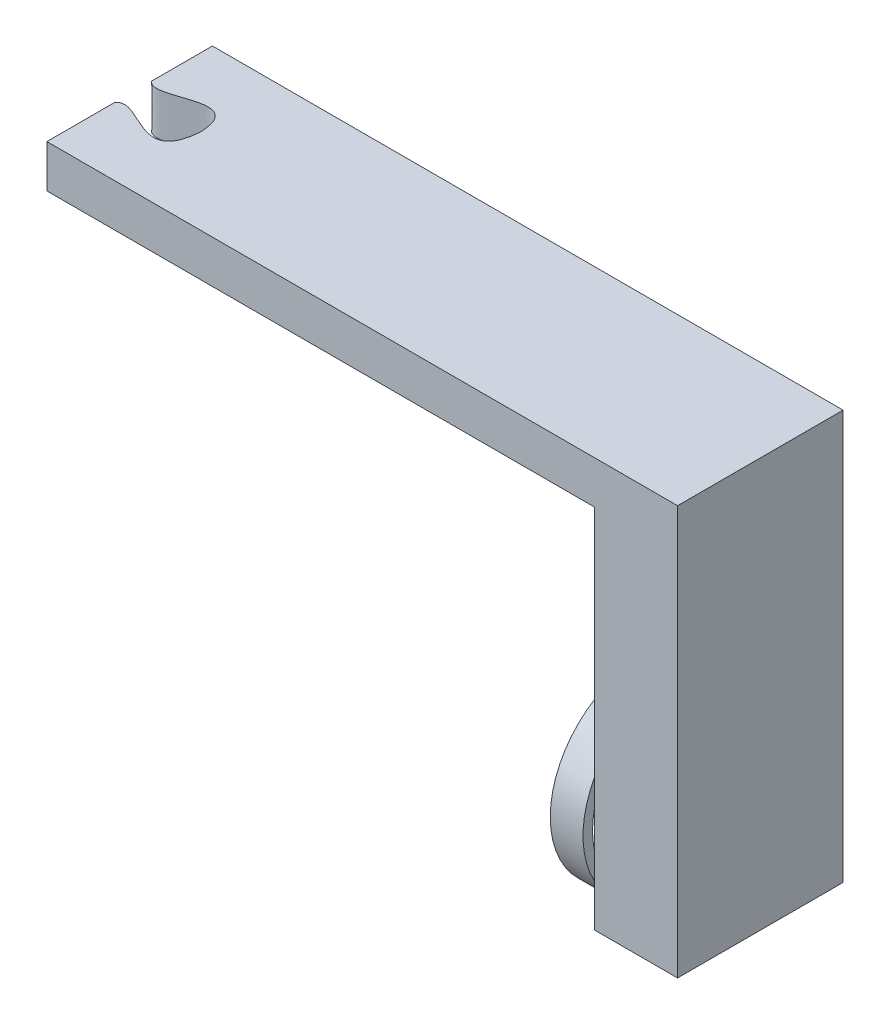
SolidWorks part; units mm, degrees
ref_plane "Front Plane" through (0, 0, 0) normal (0, 0, 1) x (1, 0, 0)
ref_plane "Top Plane" through (0, 0, 0) normal (0, 1, 0) x (1, 0, 0)
ref_plane "Right Plane" through (0, 0, 0) normal (1, 0, 0) x (0, 0, -1)
sketch "Sketch1" plane through (0, 0, 0) normal (0, 1, 0) x (1, 0, 0)
  line L0 (0, 24.5182) -> (0, 38.695)
  line L1 (0, 0) -> (147.4517, 0)
  line L2 (0, 0) -> (0, 15.7402)
  line L3 (0, 38.695) -> (147.4517, 38.695)
  line L4 (147.4517, 0) -> (147.4517, 38.695)
  spline S0 degree 3 poles (0, 24.5182) (3.0254, 20.2578) (15.7773, 32.7735) (15.9957, 19.7112) knots 0 0 0 0 1 1 1 1
  spline S1 degree 3 poles (0, 15.7402) (2.5408, 20.1382) (14.8016, 5.4523) (15.9957, 19.7112) knots 0 0 0 0 1 1 1 1
  point P7 (0, 23.1851)
  point P8 (0, 0)
  point P9 (0, 0)
  point P10 (0, 15.896)
  point P11 (0, 0)
  point P12 (0, 0)
  point P13 (0, 0)
  point P14 (0, 24.5182)
  point P15 (0, 15.7402)
extrude "Boss-Extrude1" add sketch "Sketch1" along normal blind 10
sketch "Sketch5" plane through (0, 0, 0) normal (0, -1, 0) x (1, 0, 0)
  line L0 (0, 0) -> (147.4517, 0) construction
  line L1 (147.4517, -38.695) -> (127.9987, -38.695)
  line L2 (147.4517, -38.695) -> (147.4517, 0)
  line L3 (147.4517, 0) -> (127.9987, 0)
  line L4 (127.9987, -38.695) -> (127.9987, 0)
extrude "Boss-Extrude2" add sketch "Sketch5" along normal blind 85.6305
sketch "Sketch6" plane through (127.9987, 0, 0) normal (-1, 0, 0) x (0, 0, 1)
  circle A0 centre (-19.3475, -65.278) radius 19.7806
  circle A1 centre (-19.3475, -65.278) radius 22
extrude "Boss-Extrude5" add sketch "Sketch6" along normal blind 7.6604
fillet "Fillet10" radius 2.5 1 edges at (127.9987, -65.278, -41.3475)
fillet "Fillet11" radius 2.5 1 edges at (127.9987, -87.278, -19.3475)
